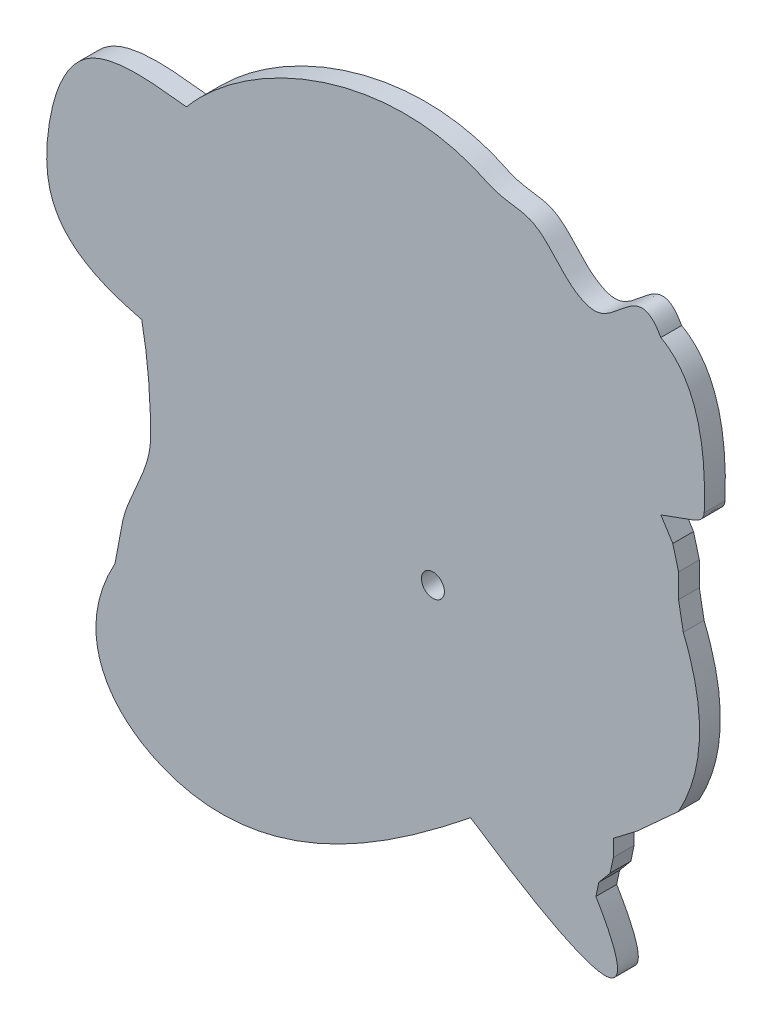
SolidWorks part; units mm, degrees
ref_plane "Front Plane" through (0, 0, 0) normal (0, 0, 1) x (1, 0, 0)
ref_plane "Top Plane" through (0, 0, 0) normal (0, 1, 0) x (1, 0, 0)
ref_plane "Right Plane" through (0, 0, 0) normal (1, 0, 0) x (0, 0, -1)
sketch "Sketch1" plane through (0, 0, 0) normal (0, 0, 1) x (1, 0, 0)
  line L0 (134.6667, 500.5) -> (673.3333, 500.5) construction
  line L9 (158.8486, 158.066) -> (159.2873, 160.158)
  line L10 (159.2873, 160.158) -> (161.0243, 162.2425)
  line L11 (161.0243, 162.2425) -> (161.5128, 164.5724)
  line L12 (161.5128, 164.5724) -> (161.5128, 167.1023)
  line L13 (161.5128, 167.1023) -> (165.1835, 169.9013)
  line L14 (165.1835, 169.9013) -> (171.472, 175.6217)
  line L15 (86.5908, 171.7678) -> (85.3882, 165.3811)
  line L16 (168.7713, 213.5075) -> (170.5915, 210.6336)
  line L17 (170.5915, 210.6336) -> (171.472, 207.3286)
  line L18 (171.472, 207.3286) -> (171.472, 203.6405)
  line L19 (171.472, 203.6405) -> (172.1964, 199.6877)
  line L21 (168.7713, 213.5075) -> (173.7621, 215.3232)
  circle A0 centre (133.9499, 186.811) radius 1.7526
  spline S0 degree 3 poles (85.3882, 165.3811) (78.0487, 152.0358) (100.0626, 129.8424) (127.3192, 149.0039) (139.7108, 158.9096) knots 0 0 0 0 0.355984 1 1 1 1
  spline S1 degree 2 poles (139.7108, 158.9096) (170.7543, 138.1113) (158.8486, 158.066) knots 0 0 0 1 1 1
  spline S2 degree 3 poles (89.473, 199.6877) (76.4141, 202.7784) (72.921, 212.6954) (79.1309, 233.8673) (92.3571, 231.6545) (96.3054, 231.2529) knots 0 0 0 0 0.435393 0.719887 1 1 1 1
  spline S3 degree 2 poles (168.7713, 236.9728) (176.0245, 232.9136) (175.3973, 217.0895) knots 0 0 0 1 1 1
  spline S4 degree 2 poles (173.7621, 215.3232) (175.2991, 215.89) (175.3973, 217.0895) knots 0 0 0 1 1 1
  spline S5 degree 3 poles (168.7713, 236.9728) (165.3483, 243.1818) (161.713, 233.5905) (153.5919, 237.311) (150.5622, 243.2925) (144.2663, 243.1727) (127.5396, 251.7095) (106.0894, 242.9451) (96.3054, 231.2529) knots 0 0 0 0 0.145953 0.187032 0.301265 0.367852 0.402075 1 1 1 1
  spline S11 degree 2 poles (172.1964, 199.6877) (177.5125, 186.6119) (171.472, 175.6217) knots 0 0 0 1 1 1
  spline S12 degree 3 poles (89.473, 199.6877) (90.4497, 194.8375) (90.826, 189.8378) (90.8383, 180.2807) (87.6783, 176.1914) (86.5908, 171.7678) knots 0 0 0 0 0.517811 0.520823 1 1 1 1
extrude "Boss-Extrude2" add sketch "Sketch1" along normal blind 3.175
